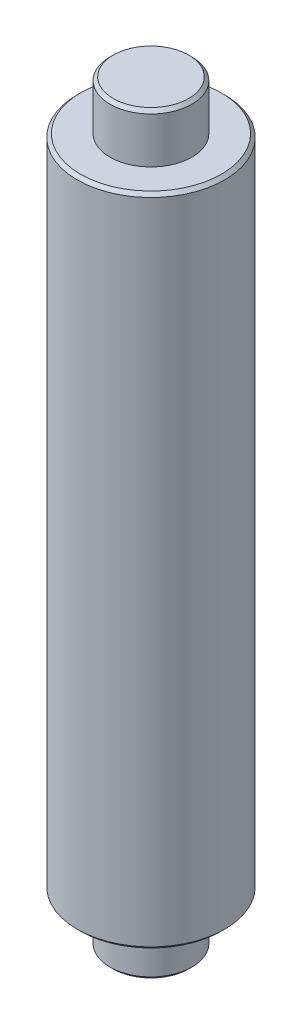
SolidWorks part; units mm, degrees
ref_plane "Front Plane" through (0, 0, 0) normal (0, 0, 1) x (1, 0, 0)
ref_plane "Top Plane" through (0, 0, 0) normal (0, 1, 0) x (1, 0, 0)
ref_plane "Right Plane" through (0, 0, 0) normal (1, 0, 0) x (0, 0, -1)
sketch "Sketch1" plane through (0, 0, 0) normal (0, 1, 0) x (1, 0, 0)
  circle A0 centre (0, 0) radius 2.5
  dimension "D1" = 5
extrude "Boss-Extrude1" add sketch "Sketch1" along normal blind 46
chamfer "Chamfer1" distance 0.2 angle 45 2 edges at (0, 46, 2.5) (0, 0, 2.5)
ref_plane "Plane1" through (0, 23, 0) normal (0, 1, 0) x (1, 0, 0)
sketch "Sketch2" plane through (0, 23, 0) normal (0, 1, 0) x (1, 0, 0)
  circle A0 centre (0, 0) radius 4.5
  dimension "D1" = 9
extrude "Boss-Extrude2" add sketch "Sketch2" along normal mid plane 40
chamfer "Chamfer2" distance 0.2 angle 45 2 edges at (0, 3, 4.5) (0, 43, 4.5)
